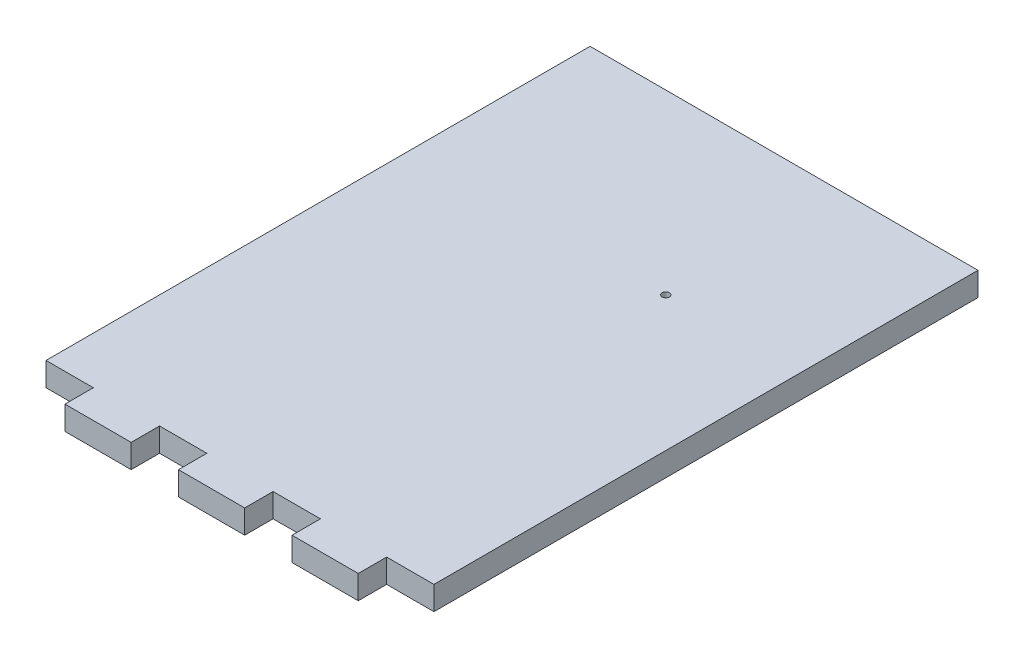
SolidWorks part; units mm, degrees
ref_plane "Alzado" through (0, 0, 0) normal (0, 0, 1) x (1, 0, 0)
ref_plane "Planta" through (0, 0, 0) normal (0, 1, 0) x (1, 0, 0)
ref_plane "Vista lateral" through (0, 0, 0) normal (1, 0, 0) x (0, 0, -1)
sketch "Croquis1" plane through (0, 0, 0) normal (0, 1, 0) x (1, 0, 0)
  line L0 (0, 0) -> (20, 0)
  line L1 (164, 230) -> (0, 230)
  line L2 (0, 230) -> (0, 0)
  line L3 (48, 0) -> (68, 0)
  line L4 (164, 230) -> (164, 0)
  line L5 (82, 230) -> (82, 130.5033) construction
  line L10 (20, 0) -> (20, -12)
  line L11 (20, -12) -> (48, -12)
  line L12 (48, 0) -> (48, -12)
  line L14 (68, 0) -> (68, -12)
  line L15 (68, -12) -> (96, -12)
  line L16 (96, 0) -> (96, -12)
  line L18 (116, 0) -> (116, -12)
  line L19 (116, -12) -> (144, -12)
  line L20 (144, 0) -> (144, -12)
  line L21 (96, 0) -> (116, 0)
  line L22 (144, 0) -> (164, 0)
  circle A0 centre (82, 215) radius 1.55
  circle A1 centre (57, 155) radius 1.55
  circle A2 centre (107, 155) radius 1.55
  circle A4 centre (62, 190) radius 3.9
  circle A5 centre (102, 190) radius 3.9
  dimension "D2" = 3.1
  dimension "D10" = 20
  dimension "D14" = 40
  dimension "D15" = 190
  dimension "D16" = 7.8
  dimension "D17" = 7.8
  dimension "D3" = 3.1
  dimension "D4" = 3.1
  dimension "D26" = 50
  dimension "D27" = 25
  dimension "D28" = 20
  dimension "D29" = 0
  dimension "D30" = 40
  dimension "D5" = 25
  dimension "D6" = 35
  dimension "D7" = 35
  dimension "D8" = 0
  dimension "D9" = 12
  dimension "D11" = 20
  dimension "D12" = 20
  dimension "D13" = 20
  dimension "D18" = 28
  dimension "D19" = 12
  dimension "D20" = 12
  dimension "D21" = 28
  dimension "D22" = 12
  dimension "D23" = 12
  dimension "D24" = 28
  dimension "D25" = 230
extrude "Saliente-Extruir1" add sketch "Croquis1" along normal blind 10 contours L2 L0 L10 L11 L12 L3 L14 L15 L16 L21 L18 L19 L20 L22 L4 L1
extrude "Cortar-Extruir1" cut sketch "Croquis1<10>" along normal blind 6 contours A4 | A5
sketch "Croquis1<10>" plane through (0, 0, 0) normal (0, 1, 0) x (1, 0, 0) same geometry as "Croquis1"
extrude "Cortar-Extruir3" cut sketch "Croquis1<11>" along normal through all contours A2
sketch "Croquis1<11>" plane through (0, 0, 0) normal (0, 1, 0) x (1, 0, 0) same geometry as "Croquis1"
